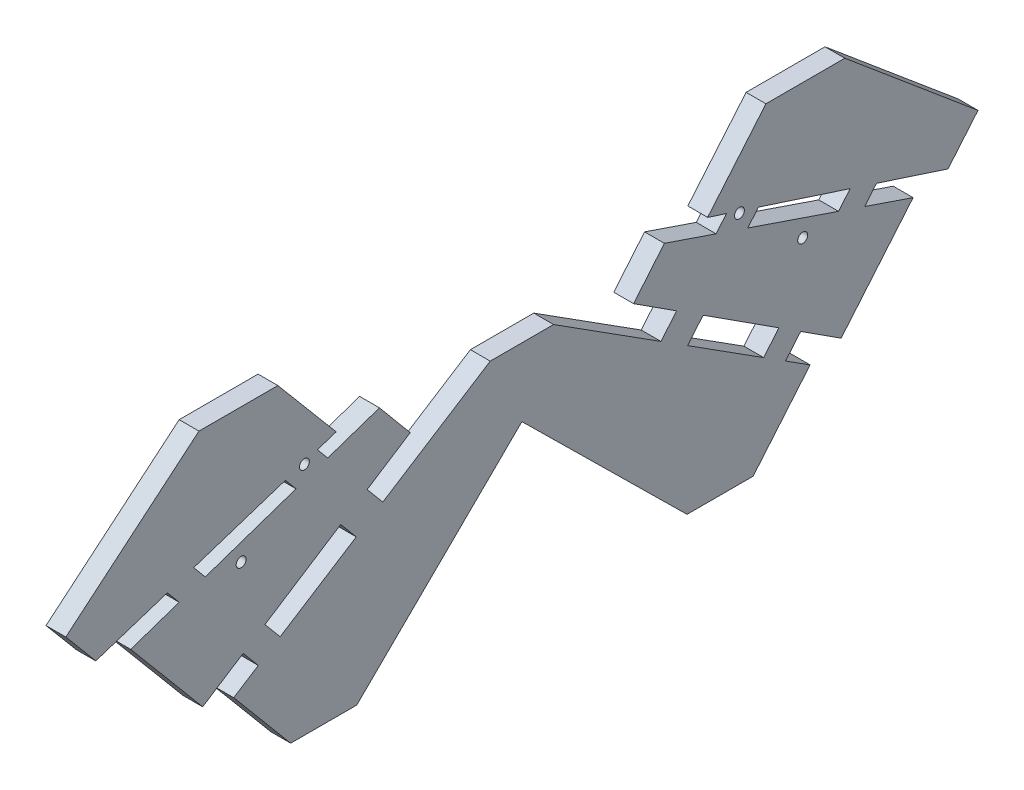
SolidWorks part; units mm, degrees
material "1060 Alloy"
ref_plane "Front Plane" through (0, 0, 0) normal (0, 0, 1) x (1, 0, 0)
ref_plane "Top Plane" through (0, 0, 0) normal (0, 1, 0) x (1, 0, 0)
ref_plane "Right Plane" through (0, 0, 0) normal (1, 0, 0) x (0, 0, -1)
sketch "Sketch1" plane through (0, 0, 0) normal (1, 0, 0) x (0, 0, -1)
  line L0 (65.8489, 71.0697) -> (85, 55) construction
  line L1 (50, 0) -> (70, 0)
  line L2 (131.2449, 61.8851) -> (104.8907, 30.4773) construction
  line L3 (131.2449, 61.8851) -> (73.0256, 110.737) construction
  line L4 (104.8907, 30.4773) -> (46.6713, 79.3292) construction
  line L5 (73.0256, 110.737) -> (46.6713, 79.3292) construction
  line L6 (97.7597, 95.7141) -> (138.0755, 61.8851)
  line L7 (138.0755, 61.8851) -> (129.0036, 51.0736)
  line L8 (129.0036, 51.0736) -> (107.3462, 58.1188)
  line L9 (120.803, 46.5093) -> (61.0516, 96.6468) construction
  line L10 (56.2246, 74.7486) -> (73.8719, 95.7141)
  line L11 (73.8719, 95.7141) -> (97.7597, 95.7141)
  line L12 (58.7828, 69.1664) -> (43.1316, 74.5033)
  line L13 (43.1316, 74.5033) -> (33.8102, 63.3371)
  line L14 (65.0961, 75.6176) -> (85.3963, 58.5837) construction
  line L15 (65.0961, 75.6176) -> (82.13, 95.9178) construction
  line L16 (85.3963, 58.5837) -> (102.4301, 78.8839) construction
  line L17 (84.3918, 30.7628) -> (96.6495, 22.8689)
  line L18 (82.13, 95.9178) -> (102.4301, 78.8839) construction
  line L19 (96.6495, 22.8689) -> (118.431, 48.827)
  line L20 (106.773, 97.945) -> (-82.0096, 97.945) construction
  line L21 (70, 0) -> (87.2542, 20.5627)
  line L22 (87.2542, 20.5627) -> (79.8082, 25.3003)
  line L23 (9.5905, 69.9777) -> (0, 69.9777)
  line L24 (0, 69.9777) -> (0, 49.3081)
  line L25 (0, 49.3081) -> (50, 0)
  line L26 (58.7828, 69.1664) -> (61.9139, 72.8979)
  line L27 (61.9139, 72.8979) -> (56.2246, 74.7486)
  line L28 (107.3462, 58.1188) -> (103.75, 53.833)
  line L29 (103.75, 53.833) -> (118.431, 48.827)
  line L30 (99.3711, 60.713) -> (95.8566, 56.5246)
  line L31 (95.8566, 56.5246) -> (68.3763, 65.8951)
  line L32 (68.3763, 65.8951) -> (71.6066, 69.7449)
  line L33 (71.6066, 69.7449) -> (99.3711, 60.713)
  line L34 (79.8082, 25.3003) -> (84.3918, 30.7628)
  line L35 (77.8013, 35.0071) -> (73.1898, 29.5114)
  line L36 (73.1898, 29.5114) -> (50.1484, 44.172)
  line L37 (50.1484, 44.172) -> (54.8568, 49.7832)
  line L38 (54.8568, 49.7832) -> (77.8013, 35.0071)
  line L39 (33.8102, 63.3371) -> (46.8468, 54.9416)
  line L40 (46.8468, 54.9416) -> (42.1045, 49.29)
  line L41 (42.1045, 49.29) -> (9.5905, 69.9777)
  circle A0 centre (85, 55) radius 1.5
  circle A1 centre (65.8489, 71.0697) radius 1.5
  circle A2 centre (85, 55) radius 3 construction
  circle A3 centre (65.8489, 71.0697) radius 3 construction
  dimension "D1" = 6
  dimension "D2" = 31
  dimension "D3" = 3
  dimension "D4" = 41
  dimension "D5" = 20
  dimension "D6" = 55
  dimension "D7" = 85
  dimension "D8" = 25
  dimension "D9" = 20
  dimension "D10" = 40
  dimension "D11" = 50
  dimension "D12" = 26.5
  dimension "D13" = 26.5
  dimension "D15" = 3.5
extrude "Boss-Extrude1" add sketch "Sketch1" along normal blind 6
hole_wizard "Tap Drill for M3 Tap1" positions "Sketch3" profile "Sketch2" hole size "M3" standard "ISO"
sketch "Sketch3" plane through (0, 0, 0) normal (0, -1, 0) x (-1, 0, 0)
  line L0 (-6, 70) -> (0, 70) construction
  line L1 (-6, 50) -> (-6, 70) construction
  point P0 (-3, 60)
  dimension "D1" = 10
  dimension "D2" = 3
sketch "Sketch2" plane through (3, 0, -60) normal (1, 0, 0) x (0, 0, -1)
  line L0 (0, 0) -> (0, 10.7511)
  line L1 (0, 10.7511) -> (1.25, 10)
  line L2 (1.25, 10) -> (1.25, 0)
  line L5 (1.25, 0) -> (0, 0)
  line L10 (0, 10.7511) -> (-1.25, 10) construction
  line L11 (0, -6.35) -> (0, 107.95) construction
  dimension "Hole Dia." = 2.5
  dimension "Hole Depth" = 10
  dimension "Drill Angle" = 118
mirror "Mirror1" about plane through (0, 0, 0) normal (0, 0, 1) of "Boss-Extrude1", "Tap Drill for M3 Tap1"
